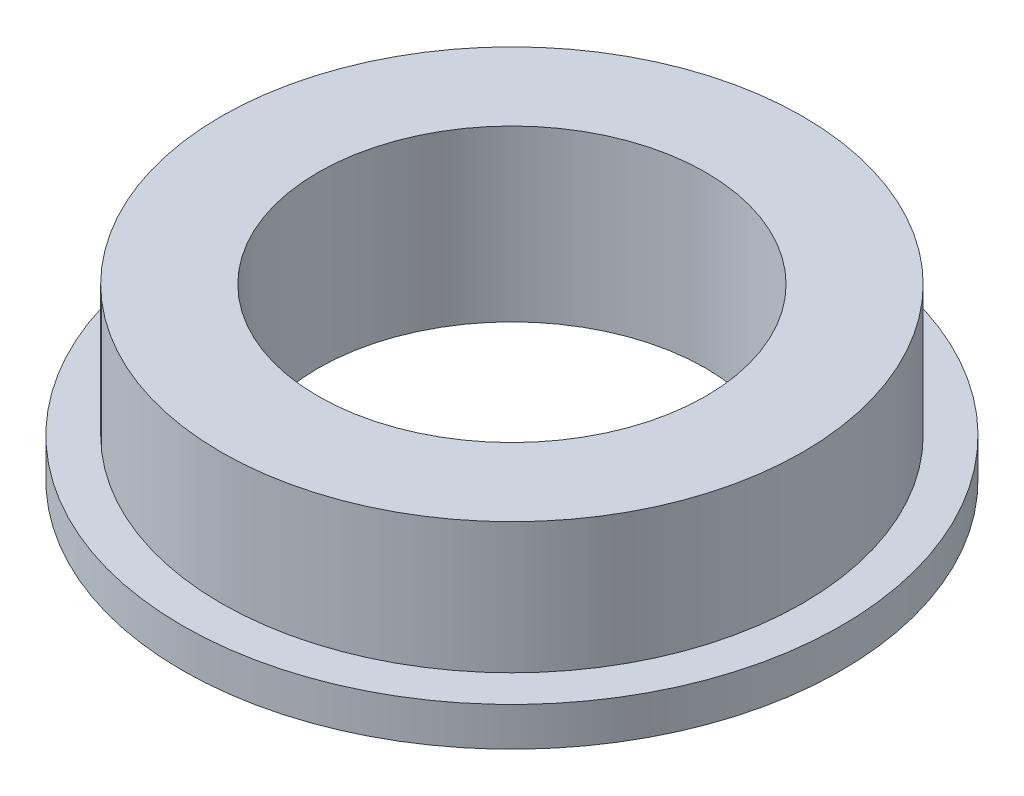
SolidWorks part; units mm, degrees
ref_plane "前视基准面" through (0, 0, 0) normal (0, 0, 1) x (1, 0, 0)
ref_plane "上视基准面" through (0, 0, 0) normal (0, 1, 0) x (1, 0, 0)
ref_plane "右视基准面" through (0, 0, 0) normal (1, 0, 0) x (0, 0, -1)
sketch "草图1" plane through (0, 0, 0) normal (0, 1, 0) x (1, 0, 0)
  circle A0 centre (0, 0) radius 6.8
  circle A1 centre (0, 0) radius 4
  circle A2 centre (0, 0) radius 6
  dimension "D1" = 8
  dimension "D2" = 13.6
  dimension "D3" = 12
extrude "凸台-拉伸1" add sketch "草图1" along normal blind 3.5 contours A2 A1 region at (-5.8303, 0, 0)
extrude "凸台-拉伸2" add sketch "草图1<3>" along normal blind 0.8 contours A0 A2 region at (-6.6077, 0, 0)
sketch "草图1<3>" plane through (0, 0, 0) normal (0, 1, 0) x (1, 0, 0) same geometry as "草图1"
